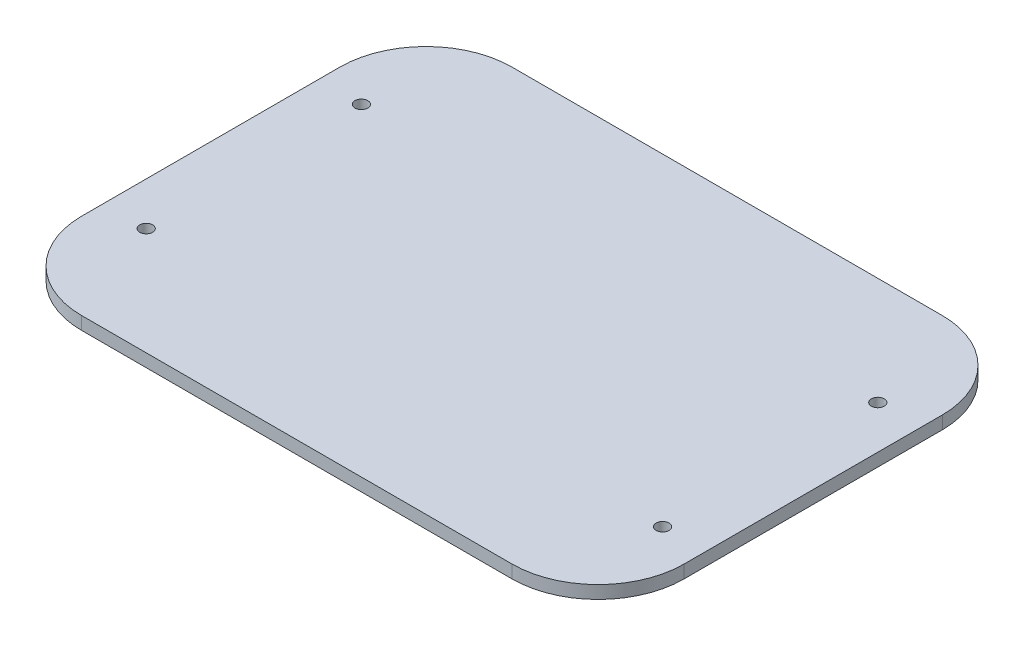
SolidWorks part; units mm, degrees
ref_plane "前视基准面" through (0, 0, 0) normal (0, 0, 1) x (1, 0, 0)
ref_plane "上视基准面" through (0, 0, 0) normal (0, 1, 0) x (1, 0, 0)
ref_plane "右视基准面" through (0, 0, 0) normal (1, 0, 0) x (0, 0, -1)
other "Configuration Table"
sketch "草图1" plane through (0, 0, 0) normal (0, 1, 0) x (1, 0, 0)
  line L1 (0, 0) -> (100, 0)
  line L2 (0, 0) -> (0, -100)
  line L3 (0, -100) -> (100, -100)
  line L4 (100, 0) -> (100, -100)
extrude "凸台-拉伸1" add sketch "草图1" along normal blind 3
sketch "草图9" plane through (0, 0, 0) normal (0, -1, 0) x (1, 0, 0)
  line L1 (100, 100) -> (120, 100)
  line L2 (100, 100) -> (100, 0)
  line L3 (100, 0) -> (120, 0)
  line L4 (120, 100) -> (120, 0)
  line L5 (0, 100) -> (-20, 100)
  line L6 (0, 100) -> (0, 0)
  line L7 (0, 0) -> (-20, 0)
  line L8 (-20, 100) -> (-20, 0)
  circle A0 centre (-10, 75) radius 1.5
  circle A1 centre (-10, 25) radius 1.5
  circle A2 centre (110, 75) radius 1.5
  circle A3 centre (110, 25) radius 1.5
extrude "凸台-拉伸5" add sketch "草图9" against normal blind 3
fillet "圆角1" radius 20 4 edges at (120, 1.5, 0) (120, 1.5, 100) (-20, 1.5, 100) (-20, 1.5, 0)
sketch "草图10" plane through (0, 0, 0) normal (0, -1, 0) x (1, 0, 0)
  line L3 (7, 50) -> (7, 0)
  line L4 (100, 0) -> (0, 0) construction
  line L5 (7, 0) -> (12, 0)
  line L6 (12, 0) -> (12, 100)
  line L7 (0, 100) -> (100, 100) construction
  line L8 (12, 100) -> (7, 100)
  line L9 (7, 100) -> (7, 50)
  line L10 (93, 50) -> (93, 0)
  line L11 (93, 0) -> (88, 0)
  line L12 (88, 0) -> (88, 100)
  line L13 (88, 100) -> (93, 100)
  line L14 (93, 100) -> (93, 50)
extrude "凸台-拉伸6" add sketch "草图10" along normal blind 7.1
sketch "草图11" plane through (0, 0, 100) normal (0, 0, 1) x (1, 0, 0)
  line L7 (7, -4.6) -> (7, -7.1)
  line L8 (7, -7.1) -> (12, -7.1)
  line L9 (12, -7.1) -> (12, -4.6)
  line L11 (88, -7.1) -> (93, -7.1)
  line L16 (93, -4.6) -> (93, -7.1)
  line L17 (88, -4.6) -> (88, -7.1)
  arc A0 (12, -4.6) -> (7, -4.6) centre (9.5, -4.6) cw
  arc A1 (88, -4.6) -> (93, -4.6) centre (90.5, -4.6) ccw
  line M8 (7, 0) -> (7, -7.1)
  line M9 (7, -7.1) -> (12, -7.1)
  line M10 (12, -7.1) -> (12, 0)
  line M12 (88, 0) -> (88, -7.1)
  line M13 (88, -7.1) -> (93, -7.1)
  line M14 (93, -7.1) -> (93, 0)
extrude "切除-拉伸5" cut sketch "草图11" against normal blind 100 contours A1 M12 M13 | A1 L11 M14 | A0 L8 M10 | A0 M9 M8 region at (7.5584, -6.5416, 100) region at (11.4416, -6.5416, 100) region at (88.5584, -6.5416, 100) region at (92.4416, -6.5416, 100)
sketch "草图12" plane through (0, 0, 0) normal (0, -1, 0) x (1, 0, 0)
  line L1 (100, 100) -> (96.8705, 100)
  line L2 (100, 100) -> (100, 80)
  line L3 (100, 80) -> (96.8705, 80)
  line L4 (96.8705, 100) -> (96.8705, 80)
  line L5 (100, 0) -> (96.8705, 0)
  line L6 (100, 0) -> (100, 20)
  line L7 (100, 20) -> (96.8705, 20)
  line L8 (96.8705, 0) -> (96.8705, 20)
extrude "凸台-拉伸7" add sketch "草图12" along normal blind 7.1
sketch "草图13" plane through (100, 0, 0) normal (1, 0, 0) x (0, 0, -1)
  line L0 (-100, -7.1) -> (-100, 0)
  line L2 (-100, -7.1) -> (-80, -7.1)
  line L3 (-20, -7.1) -> (0, -7.1)
  line L4 (0, -7.1) -> (0, 0)
  arc A0 (-80, -7.1) -> (-100, 0) centre (-80, 24.619) cw
  arc A1 (-20, -7.1) -> (0, 0) centre (-20, 24.619) ccw
extrude "切除-拉伸6" cut sketch "草图13" against normal blind 100
sketch "草图14" plane through (100, 0, 0) normal (1, 0, 0) x (0, 0, -1)
  line L1 (-100, 0) -> (3.34, 0)
  line L2 (-100, 0) -> (-100, -14.2441)
  line L3 (-100, -14.2441) -> (3.34, -14.2441)
  line L4 (3.34, 0) -> (3.34, -14.2441)
extrude "切除-拉伸7" cut sketch "草图14" against normal blind 4
sketch "草图25" plane through (88, 0, 0) normal (-1, 0, 0) x (0, 0, 1)
  line L0 (50, 0) -> (50, -3)
  line L1 (100, 0) -> (0, 0) construction
  line L2 (7.6572, -4.6) -> (92.3428, -4.6) construction
  line L3 (50, -3) -> (80, -3)
  line L4 (50, -3) -> (50, -4.6)
  line L5 (50, -4.6) -> (80, -4.6)
  line L6 (80, -3) -> (80, -4.6)
  line L8 (50, -3) -> (20, -3)
  line L9 (50, -3) -> (50, -4.6)
  line L10 (50, -4.6) -> (20, -4.6)
  line L11 (20, -3) -> (20, -4.6)
sketch "草图26" plane through (12, 0, 0) normal (1, 0, 0) x (0, 0, -1)
  line L0 (-50, 0) -> (-50, -3)
  line L1 (0, 0) -> (-100, 0) construction
  line L2 (-7.6572, -4.6) -> (-92.3428, -4.6) construction
  line L3 (-50, -3) -> (-20, -3)
  line L4 (-50, -3) -> (-50, -4.6)
  line L5 (-50, -4.6) -> (-20, -4.6)
  line L6 (-20, -3) -> (-20, -4.6)
  line L8 (-50, -3) -> (-80, -3)
  line L9 (-50, -3) -> (-50, -4.6)
  line L10 (-50, -4.6) -> (-80, -4.6)
  line L11 (-80, -3) -> (-80, -4.6)
  line M5 (-92.3428, -4.6) -> (-7.6572, -4.6)
extrude "凸台-拉伸13" add sketch "草图25" against normal blind 7 contours L8 L11 L5 L4 | L6 L3 L4 L5 region at (88, -3.8, 65) region at (88, -3.8, 35)
extrude "凸台-拉伸14" add sketch "草图26" against normal blind 7 contours L8 L11 L4 M5 | L6 L3 L4 M5 region at (12, -3.8, 35) region at (12, -3.8, 65)
fillet "圆角7" radius 10 4 edges at (95, -3.8, 20) (95, -3.8, 80) (5, -3.8, 20) (5, -3.8, 80)
equation "\"10‘\"=100"
